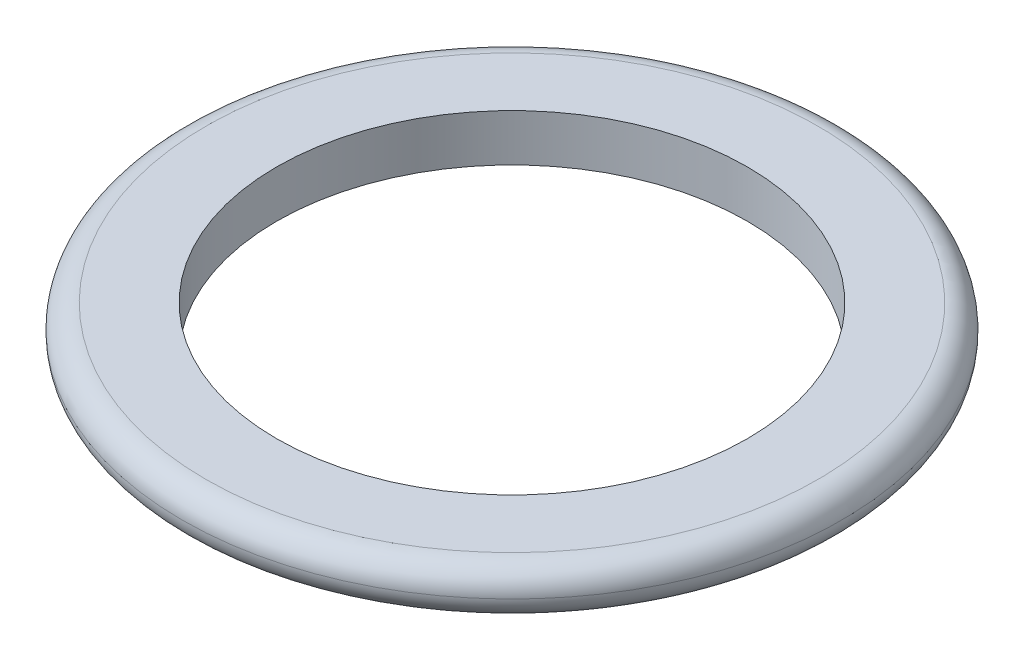
SolidWorks part; units mm, degrees
ref_plane "前视基准面" through (0, 0, 0) normal (0, 0, 1) x (1, 0, 0)
ref_plane "上视基准面" through (0, 0, 0) normal (0, 1, 0) x (1, 0, 0)
ref_plane "右视基准面" through (0, 0, 0) normal (1, 0, 0) x (0, 0, -1)
other "Configuration Table"
sketch "草图1" plane through (0, 0, 0) normal (0, 1, 0) x (1, 0, 0)
  circle A0 centre (0, 0) radius 7
  circle A1 centre (0, 0) radius 5
  dimension "D1" = 10
  dimension "D2" = 14
extrude "凸台-拉伸1" add sketch "草图1" along normal blind 1
fillet "圆角1" radius 0.5 2 edges at (0, 0, 7) (0, 1, 7)
